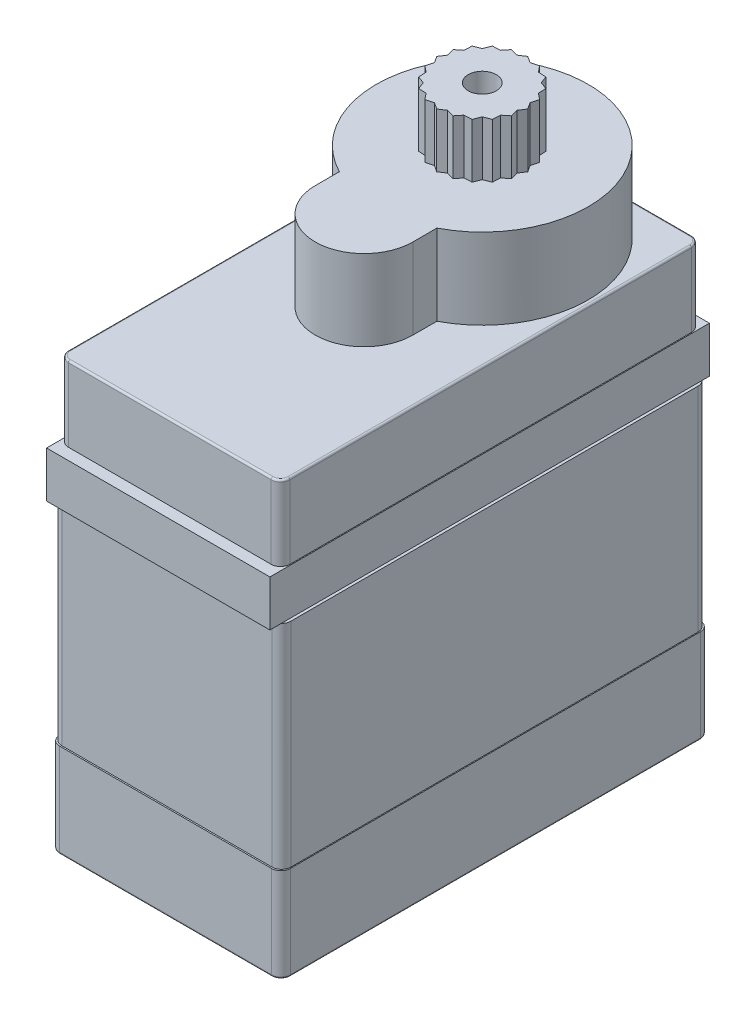
SolidWorks part; units mm, degrees
ref_plane "Ön Düzlem" through (0, 0, 0) normal (0, 0, 1) x (1, 0, 0)
ref_plane "Üst Düzlem" through (0, 0, 0) normal (0, 1, 0) x (1, 0, 0)
ref_plane "Sağ Düzlem" through (0, 0, 0) normal (1, 0, 0) x (0, 0, -1)
sketch "Çizim1" plane through (0, 0, 0) normal (0, 1, 0) x (1, 0, 0)
  line L1 (-5.65, -11.425) -> (5.65, -11.425)
  line L2 (-6.15, -10.925) -> (-6.15, 10.925)
  line L3 (-5.65, 11.425) -> (5.65, 11.425)
  line L4 (6.15, -10.925) -> (6.15, 10.925)
  line L5 (-6.15, -11.425) -> (6.15, 11.425) construction
  line L6 (-6.15, 11.425) -> (6.15, -11.425) construction
  arc A0 (-5.65, -11.425) -> (-6.15, -10.925) centre (-5.65, -10.925) cw
  arc A1 (5.65, -11.425) -> (6.15, -10.925) centre (5.65, -10.925) ccw
  arc A2 (5.65, 11.425) -> (6.15, 10.925) centre (5.65, 10.925) cw
  arc A3 (-6.15, 10.925) -> (-5.65, 11.425) centre (-5.65, 10.925) cw
  point P0 (0, 0)
  dimension "D3" = 0.5
  dimension "D1" = 22.85
  dimension "D2" = 12.3
extrude "Yükseklik-Ekstrüzyon1" add sketch "Çizim1" along normal blind 5
sketch "Çizim2" plane through (0, 5, 0) normal (0, 1, 0) x (1, 0, 0)
  line L1 (-5.6, -11.35) -> (5.6, -11.35)
  line L2 (-6.1, -10.85) -> (-6.1, 10.85)
  line L3 (-5.6, 11.35) -> (5.6, 11.35)
  line L4 (6.1, -10.85) -> (6.1, 10.85)
  line L5 (-6.1, -11.35) -> (6.1, 11.35) construction
  line L6 (-6.1, 11.35) -> (6.1, -11.35) construction
  arc A0 (5.6, -11.35) -> (6.1, -10.85) centre (5.6, -10.85) ccw
  arc A1 (-5.6, -11.35) -> (-6.1, -10.85) centre (-5.6, -10.85) cw
  arc A2 (5.6, 11.35) -> (6.1, 10.85) centre (5.6, 10.85) cw
  arc A3 (-6.1, 10.85) -> (-5.6, 11.35) centre (-5.6, 10.85) cw
  point P0 (0, 0)
  dimension "D3" = 0.5
  dimension "D1" = 22.7
  dimension "D2" = 12.2
extrude "Yükseklik-Ekstrüzyon2" add sketch "Çizim2" along normal blind 11.35
sketch "Çizim3" plane through (0, 16.35, 0) normal (0, 1, 0) x (1, 0, 0)
  line L0 (0, 20.6451) -> (0, -23.3208) construction
  line L1 (-5.45, -16.125) -> (5.45, -16.125)
  line L2 (-5.95, -15.625) -> (-5.95, 15.625)
  line L3 (-5.45, 16.125) -> (5.45, 16.125)
  line L4 (5.95, -15.625) -> (5.95, 15.625)
  line L5 (-5.95, -16.125) -> (5.95, 16.125) construction
  line L6 (-5.95, 16.125) -> (5.95, -16.125) construction
  line L7 (-0.5, 16.125) -> (-0.5, 14.991)
  line L8 (0.5, 16.125) -> (0.5, 14.991)
  line L9 (-12.4945, 0) -> (13.8323, 0) construction
  line L10 (0.5, -16.125) -> (0.5, -14.991)
  line L11 (-0.5, -16.125) -> (-0.5, -14.991)
  arc A0 (-0.5, 14.991) -> (0.5, 14.991) centre (0, 14.125) ccw
  arc A1 (-0.5, -14.991) -> (0.5, -14.991) centre (0, -14.125) cw
  arc A2 (5.45, -16.125) -> (5.95, -15.625) centre (5.45, -15.625) ccw
  arc A3 (-5.45, -16.125) -> (-5.95, -15.625) centre (-5.45, -15.625) cw
  arc A4 (-5.95, 15.625) -> (-5.45, 16.125) centre (-5.45, 15.625) cw
  arc A5 (5.45, 16.125) -> (5.95, 15.625) centre (5.45, 15.625) cw
  point P0 (0, 0)
  arc M13 (5.6, -11.35) -> (6.1, -10.85) centre (5.6, -10.85) ccw
  arc M15 (6.1, 10.85) -> (5.6, 11.35) centre (5.6, 10.85) ccw
  line M16 (5.6, 11.35) -> (-5.6, 11.35)
  arc M17 (-5.6, 11.35) -> (-6.1, 10.85) centre (-5.6, 10.85) ccw
  arc M19 (-6.1, -10.85) -> (-5.6, -11.35) centre (-5.6, -10.85) ccw
  line M20 (-5.6, -11.35) -> (5.6, -11.35)
  dimension "D5" = 1
  dimension "D6" = 0.5
  dimension "D1" = 11.9
  dimension "D2" = 32.25
  dimension "D3" = 2
  dimension "D4" = 0.5
extrude "Yükseklik-Ekstrüzyon3" add sketch "Çizim3" along normal blind 2.45 contours A5 L3 L8 A0 L7 A4 L2 L4 M17 M16 M15 | L4 L2 M13 M15 M16 M17 M19 M20 | A3 L1 L11 A1 L10 A2 L4 L2 M13 M20 M19 region at (-5.7125, 16.35, 15.8875) region at (0, 16.35, 0) region at (-5.8212, 16.35, -13.416)
sketch "Çizim4" plane through (0, 18.8, 0) normal (0, 1, 0) x (1, 0, 0)
  line L1 (-5.4, -11.2) -> (5.4, -11.2)
  line L2 (-5.9, -10.7) -> (-5.9, 10.7)
  line L3 (-5.4, 11.2) -> (5.4, 11.2)
  line L4 (5.9, -10.7) -> (5.9, 10.7)
  line L5 (-5.9, -11.2) -> (5.9, 11.2) construction
  line L6 (-5.9, 11.2) -> (5.9, -11.2) construction
  arc A0 (5.4, -11.2) -> (5.9, -10.7) centre (5.4, -10.7) ccw
  arc A1 (-5.4, -11.2) -> (-5.9, -10.7) centre (-5.4, -10.7) cw
  arc A2 (-5.9, 10.7) -> (-5.4, 11.2) centre (-5.4, 10.7) cw
  arc A3 (5.4, 11.2) -> (5.9, 10.7) centre (5.4, 10.7) cw
  point P0 (0, 0)
  dimension "D3" = 0.5
  dimension "D1" = 22.4
  dimension "D2" = 11.8
extrude "Yükseklik-Ekstrüzyon4" add sketch "Çizim4" along normal blind 4
sketch "Çizim5" plane through (0, 22.8, 0) normal (0, 1, 0) x (1, 0, 0)
  line L0 (2.6, -0.85) -> (2.6, 0.4338)
  line L1 (-2.6, -0.85) -> (-2.6, 0.4338)
  line L2 (5.4, 11.2) -> (-5.4, 11.2) construction
  line L3 (-5.4, -11.2) -> (5.4, -11.2) construction
  circle A0 centre (0, 5.45) radius 5.65
  arc A1 (-2.6, -0.85) -> (2.6, -0.85) centre (0, -0.85) ccw
  point P6 (0, -3.45)
  point P10 (0, 11.1)
  dimension "D1" = 11.3
  dimension "D2" = 2.6
  dimension "D3" = 14.65
  dimension "D4" = 22.3
extrude "Yükseklik-Ekstrüzyon5" add sketch "Çizim5" along normal blind 4.3 contours A0 | L1 A1 L0 A0 region at (0, 22.8, 1.4949) region at (0, 22.8, -5.45)
sketch "Çizim7" plane through (0, 27.1, 0) normal (0, 1, 0) x (1, 0, 0)
  line L0 (0, 7.875) -> (0.3481, 7.6476)
  line L1 (1.0101, 7.4325) -> (0.3481, 7.6476)
  line L2 (0.3481, 7.6476) -> (-0.3481, 7.6476)
  line L3 (-0.3481, 7.6476) -> (-1.0101, 7.4325)
  line L4 (-1.0101, 7.4325) -> (-1.5733, 7.0233)
  line L5 (-1.5733, 7.0233) -> (-1.9825, 6.4601)
  line L6 (-1.9825, 6.4601) -> (-2.1976, 5.7981)
  line L7 (-2.1976, 5.7981) -> (-2.1976, 5.1019)
  line L8 (-2.1976, 5.1019) -> (-1.9825, 4.4399)
  line L9 (-1.9825, 4.4399) -> (-1.5733, 3.8767)
  line L10 (-1.5733, 3.8767) -> (-1.0101, 3.4675)
  line L11 (-1.0101, 3.4675) -> (-0.3481, 3.2524)
  line L12 (-0.3481, 3.2524) -> (0.3481, 3.2524)
  line L13 (0.3481, 3.2524) -> (1.0101, 3.4675)
  line L14 (1.0101, 3.4675) -> (1.5733, 3.8767)
  line L15 (1.5733, 3.8767) -> (1.9825, 4.4399)
  line L16 (1.9825, 4.4399) -> (2.1976, 5.1019)
  line L17 (2.1976, 5.1019) -> (2.1976, 5.7981)
  line L18 (2.1976, 5.7981) -> (1.9825, 6.4601)
  line L19 (1.9825, 6.4601) -> (1.5733, 7.0233)
  line L20 (1.5733, 7.0233) -> (1.0101, 7.4325)
  line L21 (0, 7.875) -> (-0.7494, 7.7563)
  line L22 (-0.7494, 7.7563) -> (-1.4254, 7.4119)
  line L23 (-1.4254, 7.4119) -> (-1.9619, 6.8754)
  line L24 (-1.9619, 6.8754) -> (-2.3063, 6.1994)
  line L25 (-2.3063, 6.1994) -> (-2.425, 5.45)
  line L26 (-2.425, 5.45) -> (-2.3063, 4.7006)
  line L27 (-2.3063, 4.7006) -> (-1.9619, 4.0246)
  line L28 (-1.9619, 4.0246) -> (-1.4254, 3.4881)
  line L29 (-1.4254, 3.4881) -> (-0.7494, 3.1437)
  line L30 (-0.7494, 3.1437) -> (0, 3.025)
  line L31 (0, 3.025) -> (0.7494, 3.1437)
  line L32 (0.7494, 3.1437) -> (1.4254, 3.4881)
  line L33 (1.4254, 3.4881) -> (1.9619, 4.0246)
  line L34 (1.9619, 4.0246) -> (2.3063, 4.7006)
  line L35 (2.3063, 4.7006) -> (2.425, 5.45)
  line L36 (2.425, 5.45) -> (2.3063, 6.1994)
  line L37 (2.3063, 6.1994) -> (1.9619, 6.8754)
  line L38 (1.9619, 6.8754) -> (1.4254, 7.4119)
  line L39 (1.4254, 7.4119) -> (0.7494, 7.7563)
  line L40 (0.7494, 7.7563) -> (0, 7.875)
  line L41 (0.7494, 7.7563) -> (0.3481, 7.6476)
  line L42 (0.7494, 7.7563) -> (1.0101, 7.4325)
  line L43 (1.4254, 7.4119) -> (1.0101, 7.4325)
  line L44 (1.4254, 7.4119) -> (1.5733, 7.0233)
  line L45 (1.9619, 6.8754) -> (1.5733, 7.0233)
  line L46 (1.9619, 6.8754) -> (1.9825, 6.4601)
  line L47 (2.3063, 6.1994) -> (1.9825, 6.4601)
  line L48 (2.3063, 6.1994) -> (2.1976, 5.7981)
  line L49 (2.425, 5.45) -> (2.1976, 5.7981)
  line L50 (2.425, 5.45) -> (2.1976, 5.1019)
  line L51 (2.3063, 4.7006) -> (2.1976, 5.1019)
  line L52 (2.3063, 4.7006) -> (1.9825, 4.4399)
  line L53 (1.9619, 4.0246) -> (1.9825, 4.4399)
  line L54 (1.9619, 4.0246) -> (1.5733, 3.8767)
  line L55 (1.4254, 3.4881) -> (1.5733, 3.8767)
  line L56 (1.4254, 3.4881) -> (1.0101, 3.4675)
  line L57 (0.7494, 3.1437) -> (1.0101, 3.4675)
  line L58 (0.7494, 3.1437) -> (0.3481, 3.2524)
  line L59 (0, 3.025) -> (0.3481, 3.2524)
  line L60 (0, 3.025) -> (-0.3481, 3.2524)
  line L61 (-0.7494, 3.1437) -> (-0.3481, 3.2524)
  line L62 (-0.7494, 3.1437) -> (-1.0101, 3.4675)
  line L63 (-1.4254, 3.4881) -> (-1.0101, 3.4675)
  line L64 (-1.4254, 3.4881) -> (-1.5733, 3.8767)
  line L65 (-1.9619, 4.0246) -> (-1.5733, 3.8767)
  line L66 (-1.9619, 4.0246) -> (-1.9825, 4.4399)
  line L67 (-2.3063, 4.7006) -> (-1.9825, 4.4399)
  line L68 (-2.3063, 4.7006) -> (-2.1976, 5.1019)
  line L69 (-2.425, 5.45) -> (-2.1976, 5.1019)
  line L70 (-2.425, 5.45) -> (-2.1976, 5.7981)
  line L71 (-2.3063, 6.1994) -> (-2.1976, 5.7981)
  line L72 (-2.3063, 6.1994) -> (-1.9825, 6.4601)
  line L73 (-1.9619, 6.8754) -> (-1.9825, 6.4601)
  line L74 (-1.9619, 6.8754) -> (-1.5733, 7.0233)
  line L75 (-1.4254, 7.4119) -> (-1.5733, 7.0233)
  line L76 (-1.4254, 7.4119) -> (-1.0101, 7.4325)
  line L77 (-0.7494, 7.7563) -> (-1.0101, 7.4325)
  line L78 (-0.7494, 7.7563) -> (-0.3481, 7.6476)
  line L79 (0, 7.875) -> (-0.3481, 7.6476)
  circle A0 centre (0, 5.45) radius 2.225 construction
  circle A1 centre (0, 5.45) radius 2.425 construction
  circle A2 centre (0, 5.45) radius 0.75
  point P104 (0, 5.45)
  dimension "D1" = 4.45
  dimension "D2" = 4.85
  dimension "D4" = 1.5
  dimension "D3" = 20
extrude "Yükseklik-Ekstrüzyon6" add sketch "Çizim7" along normal blind 2.9 contours L19 L20 L1 L2 L3 L4 L5 L6 L7 L8 L9 L10 L11 L12 L13 L14 L15 L16 L17 L18 A2 | L78 L77 L3 | L0 L79 L2 | L76 L75 L4 | L74 L73 L5 | L72 L71 L6 | L68 L67 L8 | L70 L69 L7 | L66 L65 L9 | L64 L63 L10 | L62 L61 L11 | L60 L59 L12 | L58 L57 L13 | L42 L41 L1 | L44 L43 L20 | L46 L45 L19 | L48 L47 L18 | L50 L49 L17 | L52 L51 L16 | L54 L53 L15 | L56 L55 L14 region at (0, 27.1, -7.7234) region at (0.7025, 27.1, -7.6121) region at (0.6599, 27.1, -7.4809) region at (-0.7025, 27.1, -7.6121) region at (1.3363, 27.1, -7.2892) region at (-1.3363, 27.1, -7.2892) region at (1.8392, 27.1, -6.7863) region at (-1.8392, 27.1, -6.7863) region at (2.1621, 27.1, -6.1525) region at (-2.1621, 27.1, -6.1525) region at (2.2734, 27.1, -5.45) region at (-2.2734, 27.1, -5.45) region at (2.1621, 27.1, -4.7475) region at (-2.1621, 27.1, -4.7475) region at (1.8392, 27.1, -4.1137) region at (-1.8392, 27.1, -4.1137) region at (1.3363, 27.1, -3.6108) region at (-1.3363, 27.1, -3.6108) region at (0.7025, 27.1, -3.2879) region at (-0.7025, 27.1, -3.2879) region at (0, 27.1, -3.1766)
fillet "Radyus1" radius 0.1 16 edges at (-5.7536, 22.8, -11.0536) (0, 22.8, -11.2) (5.7536, 22.8, -11.0536) (5.9, 22.8, 0) (5.7536, 22.8, 11.0536) (0, 22.8, 11.2) (-5.7536, 22.8, 11.0536) (0, 0, 11.425) (6.0036, 0, 11.2786) (6.15, 0, 0) (6.0036, 0, -11.2786) (0, 0, -11.425) (-6.0036, 0, -11.2786) (-6.15, 0, 0) (-6.0036, 0, 11.2786) (-5.9, 22.8, 0)
sketch "Çizim8" plane through (0, 0, -11.425) normal (0, 0, -1) x (-1, 0, 0)
  line L0 (-5.65, 5) -> (5.65, 5) construction
  line L1 (-1.85, 5) -> (1.85, 5)
  line L2 (-1.85, 5) -> (-1.85, 3.8)
  line L3 (-1.85, 3.8) -> (1.85, 3.8)
  line L4 (1.85, 5) -> (1.85, 3.8)
  circle A0 centre (-1.25, 4.4) radius 0.6
  circle A1 centre (0, 4.4) radius 0.6
  circle A2 centre (1.25, 4.4) radius 0.6
  point P6 (0, 3.8)
  dimension "D1" = 3.7
  dimension "D2" = 1.2
extrude "Yükseklik-Ekstrüzyon7" add sketch "Çizim8" along normal blind 3 contours A0 | A1 | A2 region at (1.25, 4.4, -11.425) region at (0, 4.4, -11.425) region at (-1.25, 4.4, -11.425)
sketch "Sketch1" plane through (0, 18.8, 0) normal (0, 1, 0) x (1, 0, 0)
  line L0 (-5.95, -15.625) -> (-5.95, 15.625) construction
  line L1 (-5.95, 11.6051) -> (5.95, 11.6051)
  line L2 (-5.95, 11.6051) -> (-5.95, -11.8158)
  line L3 (-5.95, -11.8158) -> (5.95, -11.8158)
  line L4 (5.95, 11.6051) -> (5.95, -11.8158)
  line L5 (5.95, -15.625) -> (5.95, 15.625) construction
extrude "Cut-Extrude1" cut sketch "Sketch1" against normal up to surface (2.45 mm away) flip side to cut up to face at (0, 16.35, -14.1047)
